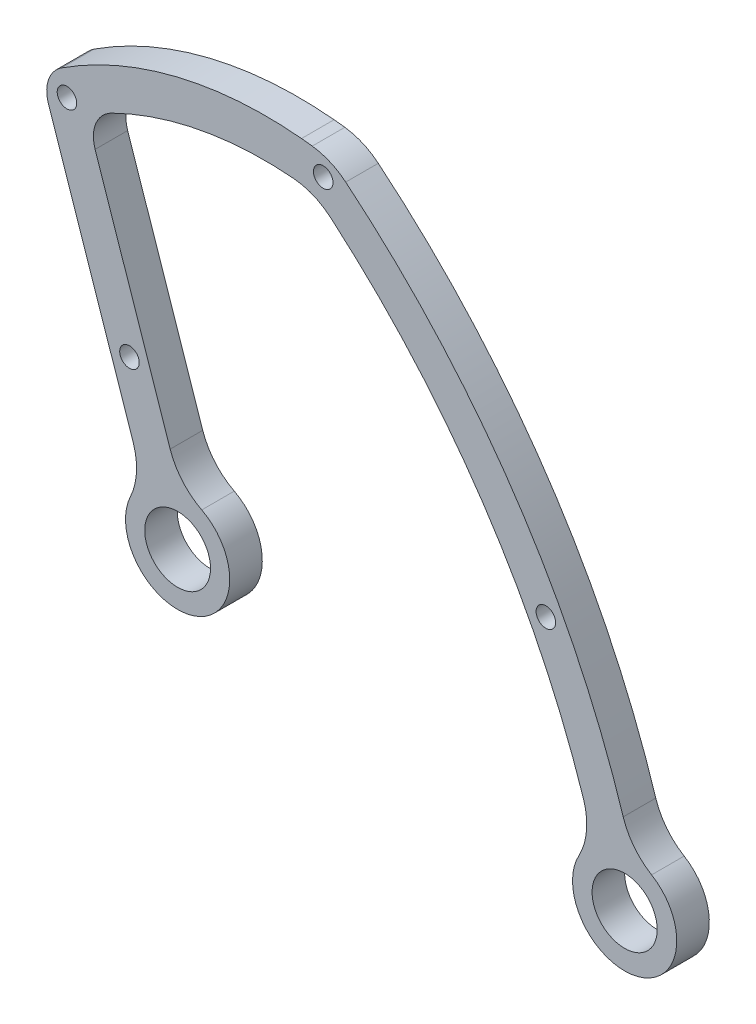
SolidWorks part; units mm, degrees
material "A2017"
ref_plane "正面" through (0, 0, 0) normal (0, 0, 1) x (1, 0, 0)
ref_plane "平面" through (0, 0, 0) normal (0, 1, 0) x (1, 0, 0)
ref_plane "右側面" through (0, 0, 0) normal (1, 0, 0) x (0, 0, -1)
sketch "ｽｹｯﾁ2" plane through (0, 0, 0) normal (0, 0, 1) x (1, 0, 0)
  line L4 (-103.4721, 101.9749) -> (-90.4656, 63.494)
  line L5 (-84.7815, 65.4152) -> (-96.3061, 99.5117)
  circle A21 centre (-100.6248, 104.2316) radius 1.5
  circle A22 centre (-61.2846, 113.3479) radius 1.5
  circle A23 centre (-91.0319, 74.5383) radius 1.5
  circle A24 centre (-83.6371, 52.6602) radius 5.05
  circle A25 centre (-27.0948, 71.9322) radius 1.5
  circle A26 centre (-15, 38.9143) radius 5
  arc A30 (-15.2219, 51.2935) -> (-57.8253, 114.4005) centre (-143.6936, 10.4967) ccw
  arc A31 (-57.8253, 114.4005) -> (-62.9665, 116.6163) centre (-64.1956, 106.6922) ccw
  arc A32 (-62.9665, 116.6163) -> (-64.6165, 116.798) centre (-70.4705, 56.0286) ccw
  arc A33 (-64.6165, 116.798) -> (-101.462, 107.7671) centre (-70.1265, 59.5994) ccw
  arc A34 (-101.462, 107.7671) -> (-103.4721, 101.9749) centre (-98.7354, 103.5759) ccw
  arc A35 (-90.8824, 56.0521) -> (-90.4656, 63.494) centre (-99.9391, 60.2919) ccw
  arc A36 (-90.8824, 56.0521) -> (-79.9353, 59.7522) centre (-83.6371, 52.6602) ccw
  arc A37 (-84.7815, 65.4152) -> (-79.9353, 59.7522) centre (-75.308, 68.6172) ccw
  arc A38 (-93.7791, 105.5979) -> (-96.3061, 99.5117) centre (-91.5694, 101.1127) ccw
  arc A39 (-65.8029, 110.8809) -> (-93.7791, 105.5979) centre (-70.2884, 57.9186) ccw
  arc A40 (-60.161, 108.5281) -> (-65.8029, 110.8809) centre (-66.6468, 100.9166) ccw
  arc A41 (-21.3117, 50.6279) -> (-60.161, 108.5281) centre (-143.6936, 10.4967) ccw
  arc A42 (-22.0284, 42.7355) -> (-21.3117, 50.6279) centre (-30.8139, 47.512) ccw
  arc A43 (-22.0284, 42.7355) -> (-10.8626, 45.7613) centre (-15, 38.9143) ccw
  arc A44 (-15.2219, 51.2935) -> (-10.8626, 45.7613) centre (-5.6909, 54.3201) ccw
extrude "ﾎﾞｽ - 押し出し1" add sketch "ｽｹｯﾁ2" along normal blind 5
